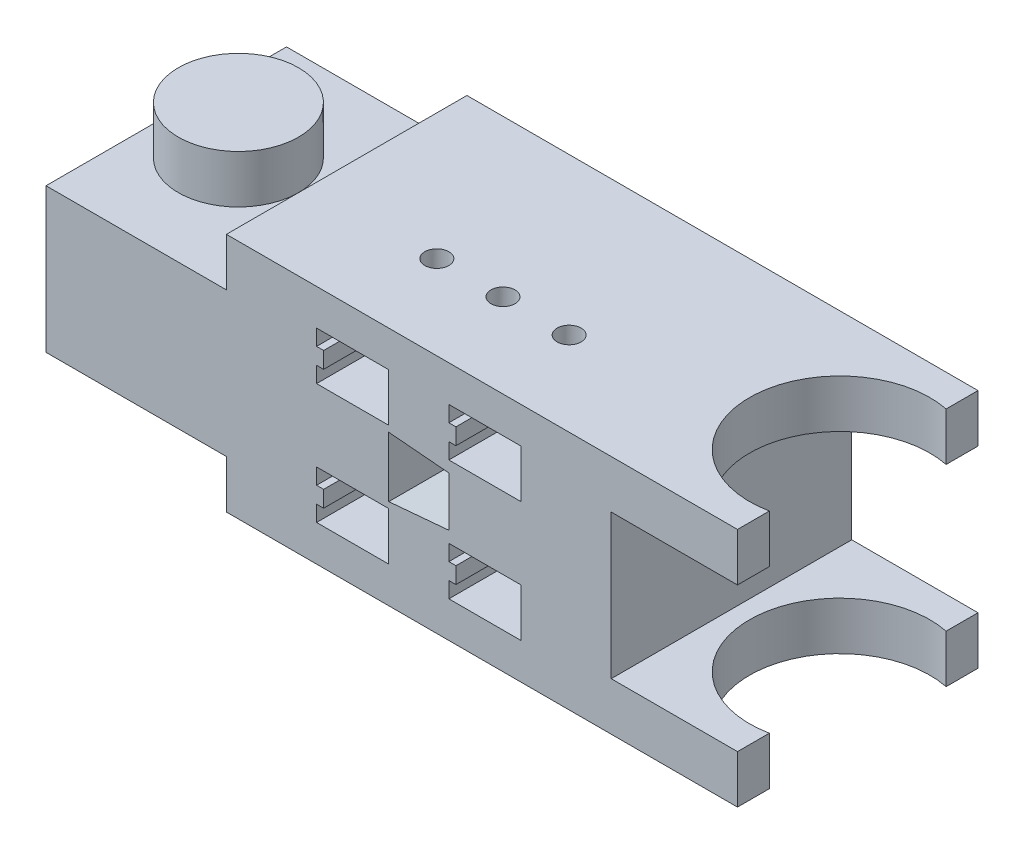
SolidWorks part; units mm, degrees
ref_plane "Front Plane" through (0, 0, 0) normal (0, 0, 1) x (1, 0, 0)
ref_plane "Top Plane" through (0, 0, 0) normal (0, 1, 0) x (1, 0, 0)
ref_plane "Right Plane" through (0, 0, 0) normal (1, 0, 0) x (0, 0, -1)
sketch "Sketch1" plane through (0, 0, 0) normal (0, 0, 1) x (1, 0, 0)
  line L0 (0, 0) -> (-19.5, 0) construction
  line L5 (-19.5, 0) -> (-30.5, 0) construction
  line L6 (-30.5, 0) -> (-50, 0) construction
  line L7 (-50, -6) -> (-42.5, -6) construction
  line L8 (-50, -10) -> (0, -10) construction
  line L9 (-50, -10) -> (-50, 10) construction
  line L10 (-50, 10) -> (0, 10) construction
  line L11 (0, -10) -> (0, 10) construction
  line L12 (-50, -10) -> (0, 10) construction
  line L13 (-50, 10) -> (0, -10) construction
  line L14 (-41, -10) -> (-41, -6)
  line L15 (-41, -6) -> (-50, -6)
  line L16 (-41, 10) -> (-41, 6)
  line L17 (-41, 6) -> (-50, 6)
  line L18 (-50, 6) -> (-56, 6)
  line L19 (-56, 6) -> (-56, -6)
  line L20 (-56, -6) -> (-50, -6)
  line L21 (-41, 10) -> (0, 10) construction
  line L22 (-41, -10) -> (0, -10)
  line L23 (0, 10) -> (1.5, 10)
  line L24 (1.5, 10) -> (1.5, 6)
  line L25 (1.5, 6) -> (0, 6)
  line L26 (0, -10) -> (1.5, -10)
  line L27 (1.5, -10) -> (1.5, -6)
  line L28 (1.5, -6) -> (0, -6)
  line L29 (0, 6) -> (0, -6) construction
  line L30 (0, 6) -> (-9, 6)
  line L31 (-9, 6) -> (-9, -6)
  line L32 (-9, -6) -> (0, -6)
  line L33 (-7.5, 0) -> (0, 0) construction
  line L34 (-7.5, 0) -> (-9, 0) construction
  line L35 (-41, 10) -> (0, 10)
  line L36 (0, 0) -> (1.5, 0) construction
  line L37 (1.5, 0) -> (1.5, 6) construction
  line L38 (-42.5, -6) -> (-41, -6) construction
  point P2 (-25, 0)
  dimension "D2" = 19.5
  dimension "D3" = 11
  dimension "D4" = 19.5
  dimension "D6" = 20
  dimension "D7" = 4
  dimension "D8" = 4
  dimension "D1" = 7.5
  dimension "D9" = 1.5
  dimension "D10" = 6
  dimension "D5" = 7.5
  dimension "D11" = 1.5
  dimension "D12" = 1.5
extrude "Boss-Extrude1" add sketch "Sketch1" along normal blind 20
sketch "Sketch2" plane through (0, -6, 0) normal (0, -1, 0) x (1, 0, 0)
  line L0 (-50, 0) -> (0, 0) construction
  line L1 (-50, 0) -> (0, 0) construction
  line L2 (-50, 0) -> (-50, 20) construction
  line L3 (-56, 20) -> (-41, 20) construction
  circle A0 centre (-50, 10) radius 5
  dimension "D1" = 10
extrude "Boss-Extrude2" add sketch "Sketch2" along normal blind 4
sketch "Sketch3" plane through (0, -10, 0) normal (0, -1, 0) x (1, 0, 0)
  line L0 (0, 0) -> (0, 20) construction
  line L1 (-41, 20) -> (1.5, 20) construction
  circle A0 centre (0, 10) radius 7.5
  dimension "D1" = 15
extrude "Cut-Extrude1" cut sketch "Sketch3" against normal up to surface (20 mm away) up to face at (-19.75, 10, 10)
mirror "Mirror1" about plane through (0, 0, 0) normal (0, 1, 0) of "Boss-Extrude2"
sketch "Sketch4" plane through (0, 0, 20) normal (0, 0, 1) x (1, 0, 0)
  line L0 (0, -10) -> (0, 10) construction
  line L1 (0, -10) -> (0, 10) construction
  line L2 (0, 0) -> (-25, 0) construction
  line L3 (-19.5, 0) -> (-30.5, 0) construction
  line L4 (-27.5, 2.5) -> (-22.5, 2.0626)
  line L5 (-27.5, -2.5) -> (-22.5, -2.5) construction
  line L6 (-27.5, -2.5) -> (-27.5, 2.5)
  line L7 (-27.5, 2.5) -> (-22.5, 2.5) construction
  line L8 (-22.5, -2.5) -> (-22.5, 2.5) construction
  line L9 (-27.5, -2.5) -> (-22.5, 2.5) construction
  line L10 (-27.5, 2.5) -> (-22.5, -2.5) construction
  line L11 (-27.5, -2.5) -> (-22.5, -2.0626)
  line L12 (-22.5, 2.0626) -> (-22.5, -2.0626)
  dimension "D1" = 5
  dimension "D2" = 5
  dimension "D3" = 25
  dimension "D4" = 5
  dimension "D5" = 5
extrude "Cut-Extrude2" cut sketch "Sketch4" against normal blind 10
sketch "Sketch5" plane through (0, 0, 20) normal (0, 0, 1) x (1, 0, 0)
  line L0 (-30.5, 0) -> (-50, 0) construction
  line L1 (-19.5, 0) -> (-30.5, 0) construction
  line L2 (0, 0) -> (-19.5, 0) construction
  line L3 (-30.5, 0) -> (-50, 0) construction
  line L4 (-19.5, 0) -> (-30.5, 0) construction
  line L5 (0, 0) -> (-19.5, 0) construction
  line L6 (-30.5, -5) -> (-30.5, 5) construction
  line L7 (-19.5, -5) -> (-19.5, 5) construction
  line L9 (-33.5, 7) -> (-27.5, 7)
  line L10 (-33.5, 7) -> (-33.5, 3)
  line L11 (-33.5, 3) -> (-27.5, 3)
  line L12 (-27.5, 7) -> (-27.5, 3)
  line L13 (-33.5, 7) -> (-27.5, 3) construction
  line L14 (-33.5, 3) -> (-27.5, 7) construction
  line L15 (-22.5, 7) -> (-16.5, 7)
  line L16 (-22.5, 7) -> (-22.5, 3)
  line L17 (-22.5, 3) -> (-16.5, 3)
  line L18 (-16.5, 7) -> (-16.5, 3)
  line L19 (-22.5, 7) -> (-16.5, 3) construction
  line L20 (-22.5, 3) -> (-16.5, 7) construction
  line L21 (-22.5, -7) -> (-16.5, -7)
  line L22 (-22.5, -7) -> (-22.5, -3)
  line L23 (-22.5, -3) -> (-16.5, -3)
  line L24 (-16.5, -7) -> (-16.5, -3)
  line L25 (-22.5, -7) -> (-16.5, -3) construction
  line L26 (-22.5, -3) -> (-16.5, -7) construction
  line L27 (-33.5, -7) -> (-27.5, -7)
  line L28 (-33.5, -7) -> (-33.5, -3)
  line L29 (-33.5, -3) -> (-27.5, -3)
  line L30 (-27.5, -7) -> (-27.5, -3)
  line L31 (-33.5, -7) -> (-27.5, -3) construction
  line L32 (-33.5, -3) -> (-27.5, -7) construction
  point P7 (-30.5, 0)
  point P10 (-19.5, 0)
  dimension "D1" = 4
  dimension "D2" = 6
  dimension "D3" = 6
extrude "Cut-Extrude3" cut sketch "Sketch5" against normal blind 10
sketch "Sketch6" plane through (0, -10, 0) normal (0, -1, 0) x (1, 0, 0)
  line L0 (-22.5, 10) -> (-16.5, 10) construction
  line L1 (-27.5, 10) -> (-22.5, 10) construction
  line L2 (-33.5, 10) -> (-27.5, 10) construction
  line L3 (-22.5, 10) -> (-16.5, 10) construction
  line L4 (-27.5, 10) -> (-22.5, 10) construction
  line L5 (-33.5, 10) -> (-27.5, 10) construction
  line L6 (-30.5, 10) -> (-30.5, 13) construction
  line L7 (-25, 10) -> (-25, 13) construction
  line L8 (-19.5, 10) -> (-19.5, 13) construction
  circle A0 centre (-30.5, 13) radius 1
  circle A1 centre (-25, 13) radius 1
  circle A2 centre (-19.5, 13) radius 1
  dimension "D1" = 3
extrude "Cut-Extrude4" cut sketch "Sketch6" against normal up to surface (20 mm away) up to face at (-14.1667, 10, 10)
chamfer "Chamfer1" distance 3 angle 45 3 edges at (-29.5, -10, 13) (-24, -10, 13) (-18.5, -10, 13)
sketch "Sketch7" plane through (0, 0, 20) normal (0, 0, 1) x (1, 0, 0)
  line L0 (-22.5, -3) -> (-22.5, -7) construction
  line L1 (-23.087, -5.6797) -> (-21.913, -5.6797)
  line L2 (-23.087, -5.6797) -> (-23.087, -4.3203)
  line L3 (-23.087, -4.3203) -> (-21.913, -4.3203)
  line L4 (-21.913, -5.6797) -> (-21.913, -4.3203)
  line L5 (-23.087, -5.6797) -> (-21.913, -4.3203) construction
  line L6 (-23.087, -4.3203) -> (-21.913, -5.6797) construction
  line L7 (-33.5, -3) -> (-33.5, -7) construction
  line L8 (-34.087, -5.6797) -> (-32.913, -5.6797)
  line L9 (-34.087, -5.6797) -> (-34.087, -4.3203)
  line L10 (-34.087, -4.3203) -> (-32.913, -4.3203)
  line L11 (-32.913, -5.6797) -> (-32.913, -4.3203)
  line L12 (-34.087, -5.6797) -> (-32.913, -4.3203) construction
  line L13 (-34.087, -4.3203) -> (-32.913, -5.6797) construction
  line L14 (-33.5, 7) -> (-33.5, 3) construction
  line L15 (-34.087, 4.3203) -> (-32.913, 4.3203)
  line L16 (-34.087, 4.3203) -> (-34.087, 5.6797)
  line L17 (-34.087, 5.6797) -> (-32.913, 5.6797)
  line L18 (-32.913, 4.3203) -> (-32.913, 5.6797)
  line L19 (-34.087, 4.3203) -> (-32.913, 5.6797) construction
  line L20 (-34.087, 5.6797) -> (-32.913, 4.3203) construction
  line L21 (-22.5, 7) -> (-22.5, 3) construction
  line L22 (-23.087, 4.3203) -> (-21.913, 4.3203)
  line L23 (-23.087, 4.3203) -> (-23.087, 5.6797)
  line L24 (-23.087, 5.6797) -> (-21.913, 5.6797)
  line L25 (-21.913, 4.3203) -> (-21.913, 5.6797)
  line L26 (-23.087, 4.3203) -> (-21.913, 5.6797) construction
  line L27 (-23.087, 5.6797) -> (-21.913, 4.3203) construction
  point P0 (-22.5, -5)
  point P7 (-33.5, -5)
  point P14 (-33.5, 5)
  point P21 (-22.5, 5)
extrude "Boss-Extrude3" add sketch "Sketch7" against normal up to surface (10 mm away) up to face at (-19.5, -5, 10)
equation "\"offset\"=5"
equation "\"x_0\"= 19.5"
equation "\"D2@Sketch1\"=\"x_0\""
equation "\"x_1\"= 11"
equation "\"D3@Sketch1\"=\"x_1\""
equation "\"x_2\"= 19.5"
equation "\"D4@Sketch1\"=\"x_2\""
equation "\"bearing_width\"= 4"
equation "\"link_width\"= 20"
equation "\"link_height\"= 20"
equation "\"D6@Sketch1\"=\"link_width\""
equation "\"D7@Sketch1\"=\"bearing_width\""
equation "\"D8@Sketch1\"=\"bearing_width\""
equation "\"D1@Boss-Extrude1\"=\"link_height\""
equation "\"D1@Boss-Extrude2\"=\"bearing_width\""
equation "\"bearing_OD\"= 15"
equation "\"bearing_ID\"= 10"
equation "\"D1@Sketch3\"=\"bearing_OD\""
equation "\"D1@Sketch1\"=\"bearing_OD\"/2"
equation "\"bearing_offset\"= 1.5"
equation "\"D9@Sketch1\"=\"bearing_offset\""
equation "\"bearing_backstop_offset\"=6"
equation "\"D10@Sketch1\"=\"bearing_backstop_offset\""
equation "\"D5@Sketch1\"=\"bearing_OD\"/2"
equation "\"D11@Sketch1\"=\"bearing_offset\""
equation "\"D12@Sketch1\"=\"bearing_offset\""
equation "\"chuck_width\"= 5"
equation "\"D4@Sketch4\"=\"chuck_width\""
equation "\"chuck_angle\"=5"
equation "\"D2@Sketch4\"=\"chuck_angle\""
equation "\"D1@Sketch4\"=\"chuck_angle\""
equation "\"chuck_length\"= 5"
equation "\"chuck_depth\"= 10"
equation "\"D1@Cut-Extrude2\"=\"chuck_depth\""
equation "\"D5@Sketch4\"=\"chuck_length\""
equation "\"chuck_distance\"=25"
equation "\"D3@Sketch4\"=\"chuck_distance\""
equation "\"post_width\"= 4"
equation "\"D1@Sketch5\"=\"post_width\""
equation "\"post_length\"=6"
equation "\"D2@Sketch5\"=\"post_length\""
equation "\"post_bearing_width\"= 6"
equation "\"D3@Sketch5\"=\"post_bearing_width\""
equation "\"post_depth\"=10"
equation "\"D1@Cut-Extrude3\"=\"post_depth\""
equation "\"pin_offset\"= 3"
equation "\"D1@Sketch6\"=\"pin_offset\""
equation "\"pin_dia\"=2"
equation "\"D2@Sketch6\"=\"pin_dia\""
equation "\"D1@Sketch2\"=\"bearing_ID\""
